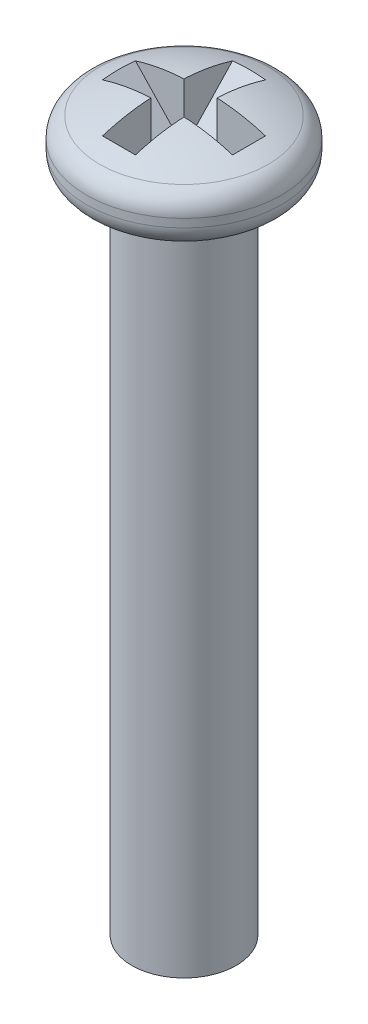
SolidWorks part; units mm, degrees
ref_plane "前视基准面" through (0, 0, 0) normal (0, 0, 1) x (1, 0, 0)
ref_plane "上视基准面" through (0, 0, 0) normal (0, 1, 0) x (1, 0, 0)
ref_plane "右视基准面" through (0, 0, 0) normal (1, 0, 0) x (0, 0, -1)
ref_axis "基准轴1" through (0, 0.5445, 0) along (0, -1, 0)
sketch "草图1" plane through (0, 0, 0) normal (1, 0, 0) x (0, 0, -1)
  line L0 (0, 0) -> (0, -19.6825) construction
  line L1 (0, 0) -> (5.696, 0) construction
  line L3 (1.775, -0.8) -> (1.775, -0.6499)
  line L4 (0.95, -1.2) -> (0.95, -13.2)
  line L5 (0.95, -13.2) -> (0, -13.2)
  line L6 (0, 0) -> (0, -13.2)
  line L7 (0, 0) -> (0, -13.2)
  line L8 (0.95, -1.2) -> (1.375, -1.2)
  arc A0 (0, 0) -> (1.5358, -0.2836) centre (0.1653, -3.4048) cw
  arc A1 (1.775, -0.6499) -> (1.5358, -0.2836) centre (1.375, -0.6499) ccw
  arc A2 (1.375, -1.2) -> (1.775, -0.8) centre (1.375, -0.8) ccw
  point P12 (1.775, -0.4)
  point P15 (1.775, -1.2)
  dimension "D5" = 0.8
  dimension "D6" = 0.4
  dimension "D7" = 0.4
  dimension "D1" = 1.9
  dimension "D2" = 12
  dimension "D3" = 3.55
  dimension "D4" = 1.2
revolve "旋转3" add sketch "草图1" angle 360 about L0
sketch "草图5" plane through (0, 0, 0) normal (1, 0, 0) x (0, 0, -1)
  line L0 (-1.8, 0.4885) -> (-0.5, -0.8839)
  line L1 (-0.5, -0.8839) -> (0.5, -0.8839)
  line L2 (0.5, -0.8839) -> (1.8, 0.4885)
  line L3 (1.8, 0.4885) -> (-1.8, 0.4885)
  line L5 (0, 0) -> (0, 1.026) construction
  dimension "D1" = 1
  dimension "D2" = 3.6
extrude "切除-拉伸1" cut sketch "草图5" against normal mid plane 0.6
pattern_circular "阵列(圆周)1" count 2 over 90 about axis through (0, 0, 0) along (0, 1, 0) of "切除-拉伸1"
ref_plane "基准面2" through (0, -0.8, 0) normal (0, 1, 0) x (-1, 0, 0)
sketch "草图6" plane through (0, -0.8, 0) normal (0, -1, 0) x (1, 0, 0)
  circle A0 centre (0, 0) radius 0.95
  dimension "D1" = 1.9
curve "螺旋线/涡状线1" parameters "D10001"=16, "D30001"=1.9, "D40001"=0.8, "D50000"=0.8
ref_plane "基准面1" through (-0.6718, -0.8, 0.6718) normal (0.7019, -0.1207, 0.7019) x (0.7106, 0.0511, -0.7018)
